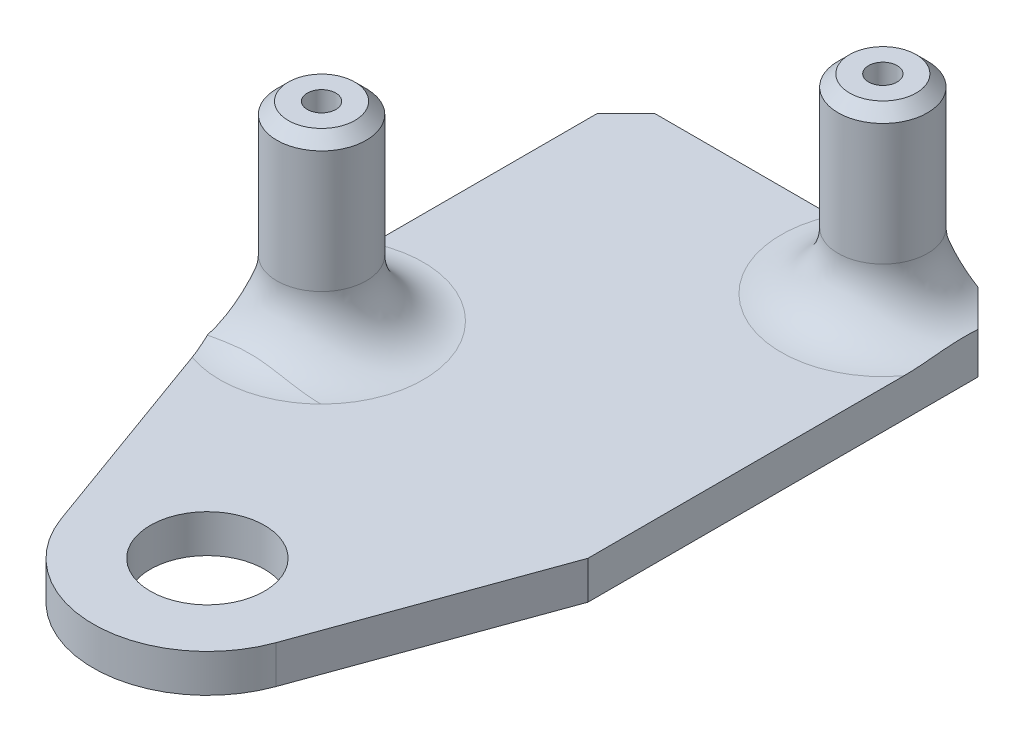
SolidWorks part; units mm, degrees
ref_plane "Front Plane" through (0, 0, 0) normal (0, 0, 1) x (1, 0, 0)
ref_plane "Top Plane" through (0, 0, 0) normal (0, 1, 0) x (1, 0, 0)
ref_plane "Right Plane" through (0, 0, 0) normal (1, 0, 0) x (0, 0, -1)
sketch "Sketch1" plane through (0, 0, 0) normal (0, 1, 0) x (1, 0, 0)
  line L1 (-2.2, 18.2) -> (17.8, 18.2)
  line L2 (-2.2, 18.2) -> (-2.2, -3.8)
  line L3 (-2.2, -3.8) -> (17.8, -3.8)
  line L4 (17.8, 18.2) -> (17.8, -3.8)
  circle A0 centre (0, 0) radius 0.75
  circle A1 centre (13.5, 16) radius 0.75
  point P9 (18.2724, -3.5956)
  dimension "D1" = 13.5
  dimension "D2" = 16
  dimension "D3" = 1.5
  dimension "D4" = 2.2
  dimension "D5" = 2.2
  dimension "D6" = 20
  dimension "D7" = 22
extrude "Boss-Extrude1" add sketch "Sketch1" along normal blind 2
sketch "Sketch2" plane through (0, 2, 0) normal (0, 1, 0) x (1, 0, 0)
  circle A0 centre (0, 0) radius 0.75 construction
  circle A1 centre (13.5, 16) radius 0.75 construction
  circle A2 centre (0, 0) radius 0.75
  circle A3 centre (13.5, 16) radius 0.75
  circle A4 centre (0, 0) radius 2.35
  circle A5 centre (13.5, 16) radius 2.35
  dimension "D1" = 1.6
extrude "Boss-Extrude2" add sketch "Sketch2" along normal blind 10
fillet "Fillet1" radius 3 2 edges at (13.5, 2, -13.65) (2.35, 2, 0)
sketch "Sketch3" plane through (0, 2, 0) normal (0, 1, 0) x (1, 0, 0)
  line L0 (3.766, -3.8) -> (17.8, -3.8) construction
  line L1 (17.8, -3.8) -> (13.4419, -15.8419)
  line L2 (-2.2, -3.8) -> (2.1581, -15.8419)
  line L3 (17.8, 7.7601) -> (-2.2, 7.7601) construction
  line L4 (17.8, -3.8) -> (17.8, 12.8168) construction
  line L5 (7.8, 7.7601) -> (7.8, -13.8) construction
  line L6 (-2.2, 18.2) -> (-2.2, 4.8767) construction
  line L7 (17.8, -3.8) -> (-2.2, -3.8)
  circle A0 centre (7.8, -13.8) radius 3
  arc A1 (2.1581, -15.8419) -> (13.4419, -15.8419) centre (7.8, -13.8) ccw
  circle A2 centre (7.8, -13.8) radius 6 construction
  dimension "D1" = 10
  dimension "D2" = 6
  dimension "D3" = 3
extrude "Boss-Extrude3" add sketch "Sketch3" against normal up to surface (2 mm away) up to face at (7.8, 0, -7.2)
fillet "Fillet2" radius 3 1 edges at (0.783, 2, 3.8)
chamfer "Chamfer1" distance 1.5 angle 45 2 edges at (17.8, 1.0227, -18.2) (-2.2, 1, -18.2)
chamfer "Chamfer2" distance 0.6 angle 45 2 edges at (0, 12, 2.35) (13.5, 12, -13.65)
